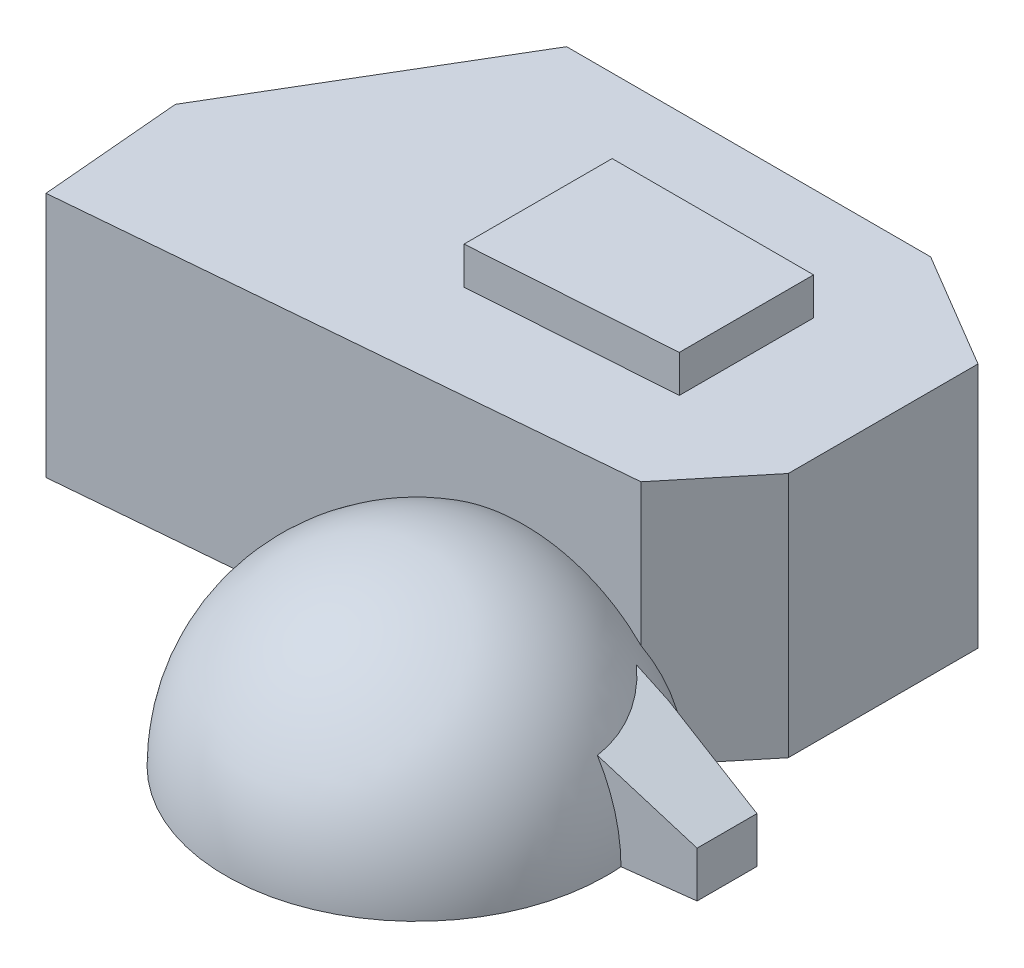
SolidWorks part; units mm, degrees
ref_plane "정면" through (0, 0, 0) normal (0, 0, 1) x (1, 0, 0)
ref_plane "윗면" through (0, 0, 0) normal (0, 1, 0) x (1, 0, 0)
ref_plane "우측면" through (0, 0, 0) normal (1, 0, 0) x (0, 0, -1)
sketch "스케치2" plane through (0, 0, 0) normal (0, 0, 1) x (1, 0, 0)
  line L0 (0, 0) -> (25.5, 0) construction
  line L1 (0, 0) -> (0, 25.5) construction
  line L2 (22.5, 0) -> (25.5, 0)
  line L3 (0, 22.5) -> (0, 25.5)
  line L4 (0, 22.5) -> (0, 25.5)
  arc A0 (22.5, 0) -> (0, 22.5) centre (0, 0) ccw
  arc A1 (25.5, 0) -> (0, 25.5) centre (0, 0) ccw
  dimension "D1" = 45
  dimension "D2" = 51
revolve "회전7" add sketch "스케치2" angle 360 about L1 region at (16.1649, 16.1649, 0)
sketch "스케치13" plane through (0, 0, 0) normal (0, -1, 0) x (1, 0, 0)
  line L0 (13.5578, -17.9565) -> (-16.4566, -15.3438)
  line L1 (-16.4566, -15.3438) -> (-55.5683, -11.9391)
  line L2 (-55.5683, -11.9391) -> (-56.8781, -26.9868)
  line L3 (-56.8781, -26.9868) -> (-38.7136, -57.6039)
  line L4 (-38.7136, -57.6039) -> (7.5532, -57.6039)
  line L5 (7.5532, -57.6039) -> (20.9807, -49.6376)
  line L6 (20.9807, -49.6376) -> (20.9807, -26.9868)
  line L7 (20.9807, -26.9868) -> (13.5578, -17.9565)
  circle A0 centre (0, 0) radius 22.5 construction
extrude "돌출-얇게3" add sketch "스케치13" against normal blind 33 thin contours L7 L0 L1 L2 L3 L4 L5 L6 thin type one direction wall 3
sketch "스케치14" plane through (0, 33, 0) normal (0, 1, 0) x (1, 0, 0)
  line L0 (-40.422, 60.6039) -> (-59.9505, 27.6878)
  line L1 (-59.9505, 27.6878) -> (-58.2968, 8.6903)
  line L2 (-58.2968, 8.6903) -> (15.0745, 15.0772)
  line L3 (15.0745, 15.0772) -> (23.9807, 25.912)
  line L4 (23.9807, 25.912) -> (23.9807, 51.346)
  line L5 (23.9807, 51.346) -> (8.3761, 60.6039)
  line L6 (-40.422, 60.6039) -> (8.3761, 60.6039) construction
  line L7 (8.3761, 60.6039) -> (-40.422, 60.6039)
extrude "보스-돌출2" add sketch "스케치14" against normal blind 3
sketch "스케치15" plane through (0, 0, 0) normal (0, -1, 0) x (1, 0, 0)
  line L0 (13.5578, -17.9565) -> (-55.5683, -11.9391)
  line L1 (-55.5683, -11.9391) -> (-56.8781, -26.9868)
  line L2 (-56.8781, -26.9868) -> (-38.7136, -57.6039)
  line L3 (-38.7136, -57.6039) -> (7.5532, -57.6039)
  line L4 (7.5532, -57.6039) -> (20.9807, -49.6376)
  line L5 (20.9807, -49.6376) -> (20.9807, -26.9868)
  line L6 (20.9807, -26.9868) -> (13.5578, -17.9565)
extrude "컷-돌출1" cut sketch "스케치15" against normal blind 30
sketch "스케치16" plane through (0, 0, 0) normal (0, 0, 1) x (1, 0, 0)
  line L0 (0, 0) -> (0, 25.5) construction
  line L1 (-25.5, 0) -> (25.5, 0) construction
  line L2 (0, 0) -> (25.5, 0) construction
  line L3 (0, 25.5) -> (0, 0)
  line L4 (0, 0) -> (25.5, 0)
  arc A0 (25.5, 0) -> (-25.5, 0) centre (0, 0) ccw construction
  arc A1 (25.5, 0) -> (0, 25.5) centre (0, 0) ccw
  arc A2 (22.5, 0) -> (0, 22.5) centre (0, 0) ccw
revolve "컷-회전1" cut sketch "스케치16" angle 360 about L0 region at (9.5493, 9.5493, 0)
sketch "스케치17" plane through (0, 0, 0) normal (0, -1, 0) x (1, 0, 0)
  line L0 (-55.5683, -11.9391) -> (-16.4566, -15.3438)
  line L1 (-16.4566, -15.3438) -> (-20.2774, -17.7248) construction
  line L2 (-20.2774, -17.7248) -> (-20.771, -18.5772) construction
  line L3 (-20.771, -18.5772) -> (-55.5683, -11.9391) construction
  spline S0 degree 3 poles (-16.4566, -15.3438) (-20.2774, -17.7248) (-20.771, -18.5772) (-55.5683, -11.9391) knots 0 0 0 0 1 1 1 1
  point P6 (-19.7351, -18.3519)
  point P7 (-23.6275, -18.8913)
  point P8 (-18.3634, -18.7457)
  point P9 (-23.442, -17.3641)
  point P10 (-20.771, -18.5772)
  point P11 (-20.2774, -17.7248)
extrude "보스-돌출3" add sketch "스케치17" against normal blind 30
sketch "스케치18" plane through (0, 33, 0) normal (0, 1, 0) x (1, 0, 0)
  line L0 (23.9807, 25.912) -> (15.0745, 15.0772)
  line L2 (7.6189, 27.6699) -> (7.6189, 45.6699)
  line L3 (7.6189, 45.6699) -> (-19.3811, 45.6699)
  line L4 (-19.3811, 25.8096) -> (-19.3811, 45.6699)
  line L5 (15.0745, 15.0772) -> (-58.2968, 8.6903)
  line L6 (-58.2968, 8.6903) -> (-59.9505, 27.6878)
  line L7 (-59.9505, 27.6878) -> (-40.422, 60.6039)
  line L8 (-40.422, 60.6039) -> (8.3761, 60.6039)
  line L9 (8.3761, 60.6039) -> (23.9807, 51.346)
  line L10 (23.9807, 51.346) -> (23.9807, 25.912)
  line L11 (-19.3811, 25.8096) -> (7.6189, 27.6699)
  dimension "D1" = 18
  dimension "D2" = 27
extrude "보스-돌출5" add sketch "스케치18" along normal blind 5 contours L4 L11 L2 L3 region at (-6.1022, 33, -36.1972)
sketch "스케치19" plane through (0, 30, 0) normal (0, -1, 0) x (1, 0, 0)
  line L0 (4.6189, -30.4703) -> (-16.3811, -29.0234)
  line L2 (4.6189, -30.4703) -> (4.6189, -42.6699)
  line L3 (4.6189, -42.6699) -> (-16.3811, -42.6699)
  line L4 (-16.3811, -30.2407) -> (-16.3811, -42.6699)
  line L5 (-16.3811, -29.0234) -> (-16.3811, -30.2407)
  line L6 (-19.3811, -25.8096) -> (-19.3811, -45.6699) construction
  line L7 (7.6189, -27.6699) -> (7.6189, -45.6699) construction
  line L8 (7.6189, -45.6699) -> (-19.3811, -45.6699) construction
  line L9 (-19.3811, -25.8096) -> (7.6189, -27.6699) construction
  point P13 (-5.8811, -26.7397)
  dimension "D1" = 3
  dimension "D2" = 3
  dimension "D3" = 3
  dimension "D4" = 0
  dimension "D5" = 3
extrude "컷-돌출3" cut sketch "스케치19" against normal blind 4
sketch "스케치27" plane through (0, 0, 0) normal (0, -1, 0) x (1, 0, 0)
  line L1 (16.8301, -1.3262) -> (34.5041, -1.3262)
  line L2 (16.8301, -1.3262) -> (16.8301, -12.3262)
  line L3 (16.8301, -12.3262) -> (34.5041, -12.3262)
  line L4 (34.5041, -1.3262) -> (34.5041, -12.3262)
  dimension "D1" = 11
extrude "보스-돌출6" add sketch "스케치27" against normal blind 15
sketch "스케치29" plane through (0, 0, 0) normal (0, -1, 0) x (1, 0, 0)
  line L0 (16.8301, -1.3262) -> (16.8301, -12.3262) construction
  line L4 (32.5041, -5.0913) -> (32.5041, -9.8262)
  line L5 (34.5041, -12.3262) -> (34.5041, -1.3262) construction
  line L8 (16.8301, -1.3262) -> (32.5041, -5.0913)
  line L9 (16.8301, -11.1541) -> (32.5041, -9.8262)
  line L10 (16.8301, -1.3262) -> (16.8301, -11.1541)
  dimension "D1" = 2
extrude "컷-돌출5" cut sketch "스케치29" against normal blind 9.5
chamfer "모따기1" distance 15 angle 20 1 edges at (32.5041, 9.5, -7.4588) first distance on face at (24.6671, 9.5, -6.8495)
sketch "스케치31" plane through (0, 0, 0) normal (0, 0, 1) x (1, 0, 0)
  line L0 (0, 0) -> (0, 22.5)
  line L1 (0, 0) -> (25.5, 0)
  line L2 (0, 0) -> (0, 25.5) construction
  circle A0 centre (0, 0) radius 25.5
  circle A1 centre (0, 0) radius 22.5
revolve "컷-회전2" cut sketch "스케치31" angle 360 about L2 region at (9.5493, 9.5493, 0)
chamfer "모따기2" distance 15 angle 7 1 edges at (34.5041, 7.5, -1.3262) first distance on face at (29.0609, 7.597, -1.3262)
chamfer "모따기3" distance 13 angle 5 1 edges at (34.5041, 7.5, -12.3262) first distance on face at (25.2639, 9.0325, -12.3262)
chamfer "모따기4" distance 19 angle 25 1 edges at (34.5041, 15, -7.1784) first distance on face at (24.2433, 15, -8.7732)
